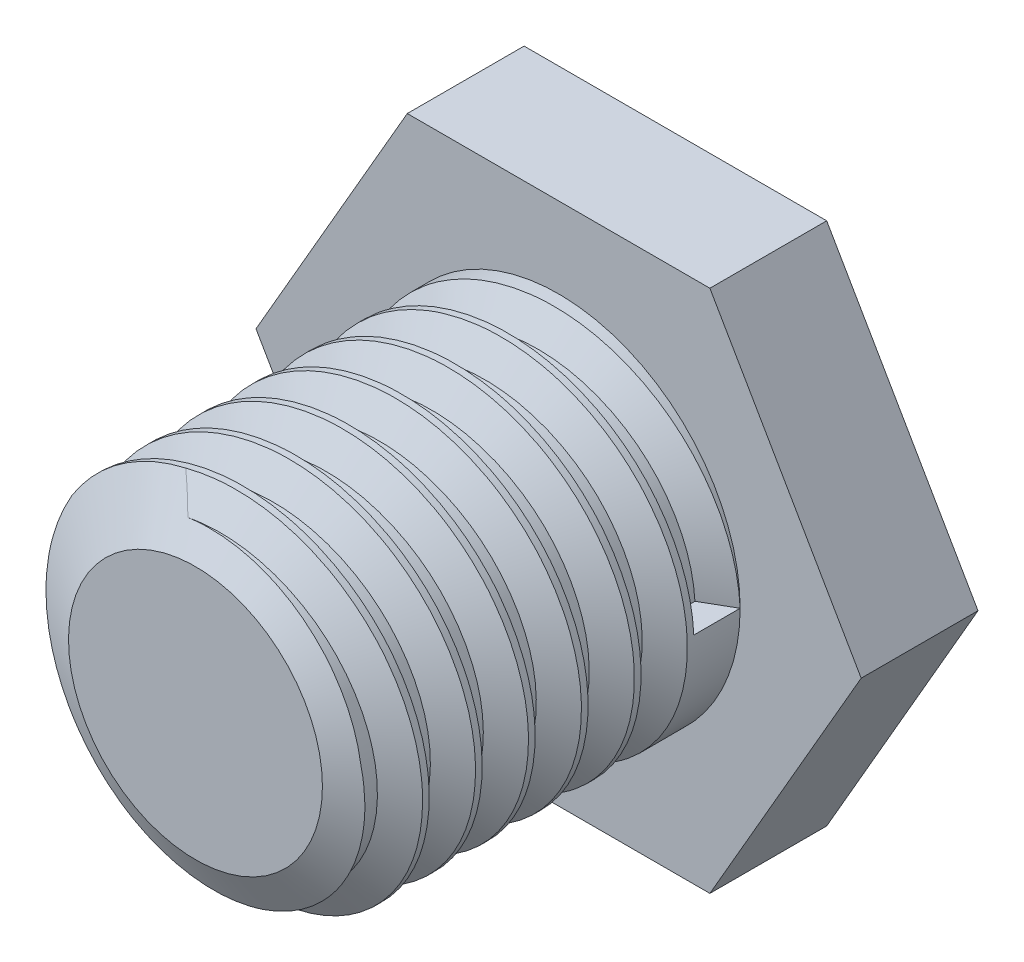
SolidWorks part; units mm, degrees
ref_plane "Alzado" through (0, 0, 0) normal (0, 0, 1) x (1, 0, 0)
ref_plane "Planta" through (0, 0, 0) normal (0, 1, 0) x (1, 0, 0)
ref_plane "Vista lateral" through (0, 0, 0) normal (1, 0, 0) x (0, 0, -1)
sketch "Croquis1" plane through (0, 0, 0) normal (0, 0, 1) x (1, 0, 0)
  line L1 (10, 0) -> (5, 8.6603)
  line L2 (5, 8.6603) -> (-5, 8.6603)
  line L3 (-5, 8.6603) -> (-10, 0)
  line L4 (-10, 0) -> (-5, -8.6603)
  line L5 (-5, -8.6603) -> (5, -8.6603)
  line L6 (5, -8.6603) -> (10, 0)
  circle A0 centre (0, 0) radius 8.6603 construction
  circle A1 centre (0, 0) radius 6
  dimension "D2" = 12
  dimension "D1" = 10
extrude "Saliente-Extruir1" add sketch "Croquis1" along normal blind 5.0623 contours L1 L2 L3 L4 L5 L6
sketch "Croquis2" plane through (0, 0, 5.0623) normal (0, 0, 1) x (1, 0, 0)
  line L6 (10, 0) -> (5, 8.6603)
  line L7 (5, 8.6603) -> (-5, 8.6603)
  line L8 (-5, 8.6603) -> (-10, 0)
  line L9 (-10, 0) -> (-5, -8.6603)
  line L10 (-5, -8.6603) -> (5, -8.6603)
  line L11 (5, -8.6603) -> (10, 0)
  line L12 (10, 0) -> (5, 8.6603)
  circle A1 centre (0, 0) radius 6
  circle A2 centre (0, 0) radius 6
  dimension "D1" = 0
  dimension "D2" = 0
extrude "Saliente-Extruir2" add sketch "Croquis2" along normal blind 12 contours A2
chamfer "Chaflán1" distance 1 angle 61 1 edges at (6, 0, 17.0623) first distance on face at (6, 0, 17.0623)
thread "Rosca1" pitch 1.75 method cut profile "Perfil de rosca3" start angle 0, offset 0, length 18.4, pitch 1.75, diameter 12
ref_plane "Plano3" through (6, 0, 5.0623) normal (0, -1, 0) x (1, 0, 0)
sketch "Perfil de rosca3" plane through (6, 0, 5.0623) normal (0, -1, 0) x (1, 0, 0)
  line L0 (0, 0) -> (0, 1.75) construction
  line L11 (0, 0) -> (0, 1.5312)
  line L12 (0, 1.5312) -> (-0.9472, 0.9844)
  line L13 (-0.9472, 0.9844) -> (-0.9472, 0.5469)
  line L15 (-0.9472, 0.5469) -> (0, 0)
  line L17 (-0.9472, 0.7656) -> (0, 0.7656) construction
  point P2 (0, 0)
  dimension "Pitch" = 1.75
  dimension "Profile_Angle" = 60
  dimension "Profile_Land" = 0.4375
  dimension "Profile_Height" = 0.9472
chamfer "Chaflán2" distance 2 angle 31 6 edges at (7.5, 4.3301, 0) (0, 8.6603, 0) (-7.5, 4.3301, 0) (-7.5, -4.3301, 0) (0, -8.6603, 0) (7.5, -4.3301, 0) first distance on face at (0, 0, 0)
